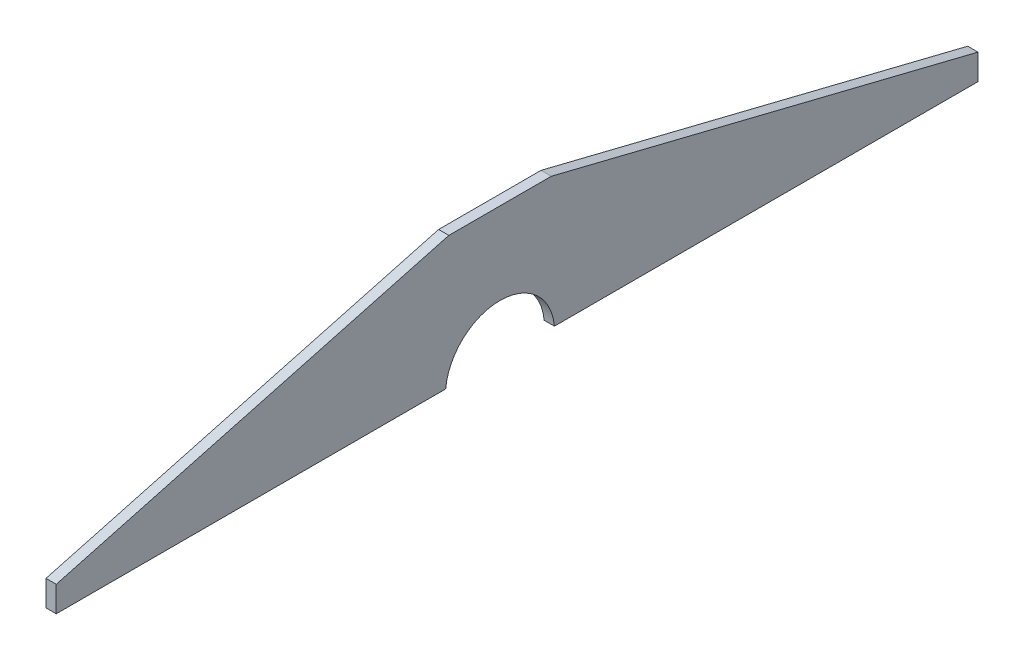
SolidWorks part; units mm, degrees
material "AISI 304"
ref_plane "Front Plane" through (0, 0, 0) normal (0, 0, 1) x (1, 0, 0)
ref_plane "Top Plane" through (0, 0, 0) normal (0, 1, 0) x (1, 0, 0)
ref_plane "Right Plane" through (0, 0, 0) normal (1, 0, 0) x (0, 0, -1)
sketch "Sketch1" plane through (0, 0, 0) normal (1, 0, 0) x (0, 0, -1)
  line L0 (-31.8591, 3) -> (-260, 3)
  line L1 (-260, 3) -> (-260, 18)
  line L2 (-260, 18) -> (-30, 80)
  line L3 (-30, 80) -> (30, 80)
  line L4 (30, 80) -> (280, 18)
  line L5 (280, 18) -> (280, 3)
  line L6 (280, 3) -> (31.8591, 3)
  arc A0 (31.8591, 3) -> (-31.8591, 3) centre (0, 0) ccw
  point P12 (0, 80)
  dimension "D1" = 64
  dimension "D2" = 15
  dimension "D3" = 15
  dimension "D4" = 60
  dimension "D5" = 80
  dimension "D6" = 260
  dimension "D7" = 280
  dimension "D8" = 3
base flange "Base-Flange1" sketch "Sketch1" thickness 6 reverse thickness direction no parameters "D1"=0
sketch "Bend-Lines1" [suppressed] plane through (0, 0, 0) normal (0, 1, 0) x (1, 0, 0)
sketch "Bounding-Box1" [suppressed] plane through (0, 0, 0) normal (0, 1, 0) x (1, 0, 0)
sheet metal parameters "Sheet-Metal3" thickness 6 parameters "D1"=0
flat pattern "Flat-Pattern3" [suppressed]
sketch "Bend-Lines2" plane through (0, 0, 0) normal (0, 1, 0) x (1, 0, 0)
sketch3d "Bounding-Box2" [suppressed]
  line L0 (-260, 3, 0) -> (280, 3, 0) construction
  line L1 (-260, 80, 0) -> (280, 80, 0) construction
  line L2 (-260, 3, 0) -> (-260, 80, 0) construction
  line L3 (280, 3, 0) -> (280, 80, 0) construction
